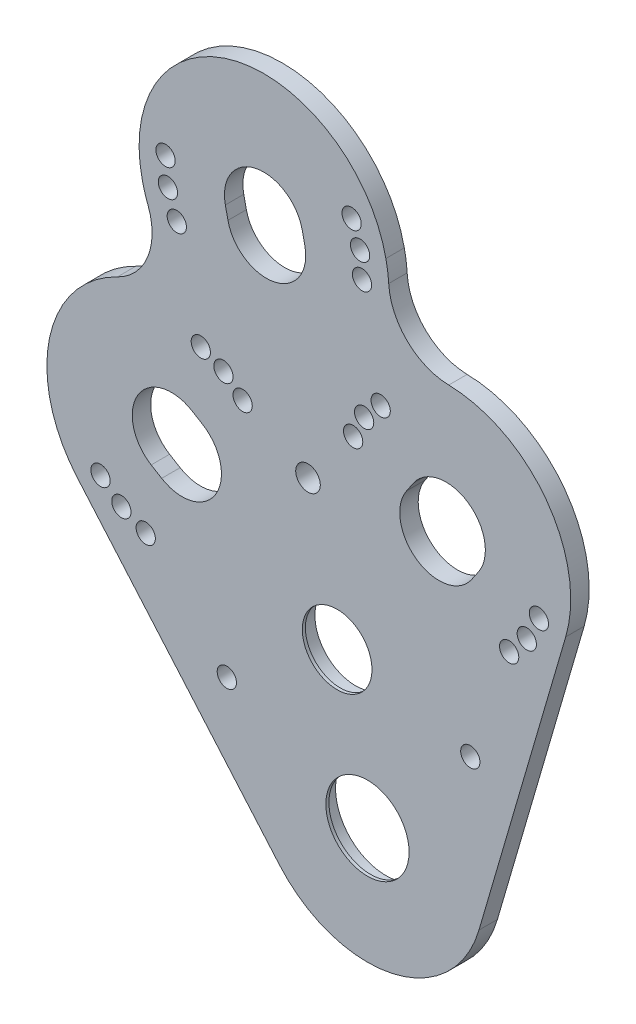
SolidWorks part; units mm, degrees
material "6061-T6 (SS)"
ref_plane "Front Plane" through (0, 0, 0) normal (0, 0, 1) x (1, 0, 0)
ref_plane "Top Plane" through (0, 0, 0) normal (0, 1, 0) x (1, 0, 0)
ref_plane "Right Plane" through (0, 0, 0) normal (1, 0, 0) x (0, 0, -1)
sketch "Sketch1" plane through (0, 0, 0) normal (0, 0, 1) x (1, 0, 0)
  line L0 (-7.8325, 36.0395) -> (0, 0) construction
  line L1 (-114.3559, 29.5275) -> (95.9028, 29.5275) construction
  line L2 (-107.2972, 26.9875) -> (95.9028, 26.9875) construction
  line L3 (-34.299, 122.3851) -> (-30.7317, 35.1036)
  line L4 (-107.2972, -23.8125) -> (95.9028, -23.8125) construction
  line L5 (-19.5919, 125.5814) -> (13.3895, 44.6925)
  line L6 (-55.9402, 56.7468) -> (-25.1916, 21.0759)
  line L7 (14.1715, 29.6307) -> (27.3408, 74.8464)
  line L8 (-50.1538, 61.7347) -> (-7.8325, 36.0395) construction
  line L9 (-7.8325, 36.0395) -> (-26.6659, 122.6971) construction
  line L10 (-7.8325, 36.0395) -> (20.0062, 76.9827) construction
  line L11 (-48.8132, 69.2556) -> (-16.6236, 63.5179)
  line L12 (-11.2396, 64.688) -> (15.6649, 83.2687)
  line L14 (-26.6659, 122.6971) -> (-26.7738, 123.1935) construction
  line L15 (-50.1538, 61.7347) -> (-50.588, 61.9983) construction
  line L16 (-22.7158, -19.6015) -> (-74.972, 40.9574)
  line L17 (28.8025, -8.4049) -> (51.2095, 68.3806)
  line L18 (-51.5405, 117.551) -> (-1.8993, 128.3396) construction
  line L19 (-49.2446, 111.0625) -> (-4.0872, 134.3316) construction
  line L20 (-52.1448, 124.407) -> (-1.4028, 121.9799) construction
  line L21 (3.4137, 96.2141) -> (36.5986, 57.7512) construction
  line L22 (-57.2674, 37.3512) -> (-43.0402, 86.1182) construction
  line L23 (-68.9403, 44.4384) -> (-32.2357, 79.5583) construction
  line L24 (-37.1888, 83.5781) -> (-63.553, 40.155) construction
  line L25 (-50.588, 61.9983) -> (-47.8741, 60.3506) construction
  line L26 (-45.3152, 70.683) -> (-42.6012, 69.0352)
  line L27 (-55.8609, 53.3137) -> (-53.1469, 51.666)
  line L28 (-26.7738, 123.1935) -> (-26.0995, 120.0909) construction
  line L29 (-16.8456, 125.3512) -> (-16.1713, 122.2486)
  line L30 (-36.702, 121.0358) -> (-36.0278, 117.9332)
  line L31 (20.0062, 76.9827) -> (20.2918, 77.4027) construction
  line L32 (-0.8556, 91.4744) -> (41.1535, 62.911) construction
  line L33 (-3.6935, 85.7615) -> (44.277, 69.044) construction
  line L34 (20.2918, 77.4027) -> (18.5066, 74.7772) construction
  line L35 (28.6936, 71.6901) -> (26.9084, 69.0645)
  line L36 (11.89, 83.1154) -> (10.1047, 80.4899)
  circle A0 centre (0, 0) radius 27.94 construction
  circle A1 centre (-7.8325, 36.0395) radius 15.24 construction
  circle A2 centre (-7.8325, 36.0395) radius 8.89 construction
  circle A3 centre (0, 0) radius 21.59 construction
  circle A4 centre (-50.1538, 61.7347) radius 32.2072 construction
  circle A5 centre (20.0062, 76.9827) radius 32.2072 construction
  circle A6 centre (-26.6659, 122.6971) radius 32.2072
  arc A7 (-25.1916, 21.0759) -> (14.1715, 29.6307) centre (-7.8325, 36.0395) ccw
  arc A8 (-48.8132, 69.2556) -> (-55.9402, 56.7468) centre (-50.1538, 61.7347) ccw
  arc A9 (27.3408, 74.8464) -> (15.6649, 83.2687) centre (20.0062, 76.9827) ccw
  arc A10 (-19.5919, 125.5814) -> (-34.299, 122.3851) centre (-26.6659, 122.6971) ccw
  circle A11 centre (-15.3533, 70.6445) radius 3.175
  arc A12 (-16.6236, 63.5179) -> (-11.2396, 64.688) centre (-15.3533, 70.6445) ccw
  arc A13 (-30.7317, 35.1036) -> (13.3895, 44.6925) centre (-7.8325, 36.0395) ccw
  circle A14 centre (-26.7738, 123.1935) radius 32.2072
  circle A15 centre (-26.7199, 122.9453) radius 32.2072 construction
  circle A16 centre (-50.588, 61.9983) radius 32.2072
  circle A17 centre (-50.3709, 61.8665) radius 32.2072 construction
  arc A18 (5.4875, 124.5569) -> (20.9913, 109.6024) centre (21.336, 125.4736) ccw
  arc A19 (-64.5891, 91.0031) -> (-56.6909, 111.0436) centre (-71.4903, 105.2995) ccw
  circle A20 centre (-36.3191, 15.6028) radius 9.525 construction
  circle A21 centre (26.5668, 29.2699) radius 9.525 construction
  arc A22 (-22.7158, -19.6015) -> (28.8025, -8.4049) centre (0, 0) ccw
  circle A23 centre (-7.8325, 36.0395) radius 10.5
  circle A24 centre (0, 0) radius 13
  circle A25 centre (0, 0) radius 8.5 construction
  circle A26 centre (0, 0) radius 12 construction
  circle A27 centre (-7.8325, 36.0395) radius 8.5 construction
  arc A28 (-45.3152, 70.683) -> (-55.8609, 53.3137) centre (-50.588, 61.9983) ccw
  arc A29 (-53.1469, 51.666) -> (-42.6012, 69.0352) centre (-47.8741, 60.3506) ccw
  arc A30 (-16.8456, 125.3512) -> (-36.702, 121.0358) centre (-26.7738, 123.1935) ccw
  arc A31 (-36.0278, 117.9332) -> (-16.1713, 122.2486) centre (-26.0995, 120.0909) ccw
  arc A32 (28.6936, 71.6901) -> (11.89, 83.1154) centre (20.2918, 77.4027) ccw
  circle A33 centre (-15.3533, 70.6445) radius 3.7158 construction
  arc A34 (-69.7639, 36.1219) -> (-70.3006, 35.5438) centre (-70.0002, 35.803) ccw
  circle A35 centre (20.149, 77.1927) radius 32.2072 construction
  circle A36 centre (20.2918, 77.4027) radius 32.2072
  arc A37 (10.1047, 80.4899) -> (26.9084, 69.0645) centre (18.5066, 74.7772) ccw
  arc A38 (49.2064, 61.5164) -> (48.4781, 61.8196) centre (48.8254, 61.6276) ccw
  circle A39 centre (-7.8325, 36.0395) radius 9
  circle A40 centre (0, 0) radius 10.75
  point P64 (-26.7199, 122.9453)
  point P66 (-51.5405, 117.551)
  point P67 (-1.8993, 128.3396)
  point P69 (-26.6659, 122.6971)
  point P71 (-49.2446, 111.0625)
  point P72 (-4.0872, 134.3316)
  point P74 (-26.7738, 123.1935)
  point P76 (-52.1448, 124.407)
  point P77 (-1.4028, 121.9799)
  point P79 (20.0062, 76.9827)
  point P81 (3.4137, 96.2141)
  point P82 (36.5986, 57.7512)
  point P88 (-50.588, 61.9983)
  point P89 (-68.9403, 44.4384)
  point P90 (-57.2674, 37.3512)
  point P91 (-63.553, 40.155)
  point P92 (-37.1888, 83.5781)
  point P93 (-43.0402, 86.1182)
  point P94 (-32.2357, 79.5583)
  point P95 (-50.3709, 61.8665)
  point P96 (-50.1538, 61.7347)
  point P98 (-49.231, 61.1745)
  point P104 (-26.4367, 121.6422)
  point P120 (20.149, 77.1927)
  point P121 (20.2918, 77.4027)
  point P122 (19.3992, 76.09)
  point P123 (-0.8556, 91.4744)
  point P124 (-3.6935, 85.7615)
  point P125 (41.1535, 62.911)
  point P126 (44.277, 69.044)
  point P135 (-36.3191, 15.6028)
  point P136 (26.5668, 29.2699)
  point P137 (-15.3533, 70.6445)
  dimension "D1" = 55.88
  dimension "D2" = 43.18
  dimension "D3" = 17.78
  dimension "D4" = 30.48
  dimension "D10" = 64.4144
  dimension "D11" = 45.8366
  dimension "D12" = 15.2789
  dimension "D16" = 92.949
  dimension "D18" = 6.35
  dimension "D19" = 14.478
  dimension "D20" = 252
  dimension "D9" = 45.8366
  dimension "D23" = 0.254
  dimension "D22" = 276
  dimension "D25" = 31.75
  dimension "D26" = 30.0037
  dimension "D27" = 19.05
  dimension "D31" = 26
  dimension "D30" = 21
  dimension "D32" = 17
  dimension "D33" = 24
  dimension "D34" = 17
  dimension "D38" = 15
  dimension "D40" = 10.16
  dimension "D42" = 10.16
  dimension "D44" = 15
  dimension "D45" = 0.7937
  dimension "D49" = 10.16
  dimension "D50" = 0.7937
  dimension "D51" = 18
  dimension "D52" = 21.5
  dimension "D5" = 36.8808
  dimension "D6" = 26.9875
  dimension "D7" = 50.8
  dimension "D8" = 2.54
  dimension "D13" = 49.5109
  dimension "D14" = 49.5109
  dimension "D15" = 123
  dimension "D17" = 46.475
  dimension "D21" = 140.868
  dimension "D24" = 0.254
  dimension "D28" = 12.7
  dimension "D29" = 12.7
  dimension "D35" = 50.8
  dimension "D36" = 15
  dimension "D37" = 15
  dimension "D39" = 15
  dimension "D41" = 3.175
  dimension "D43" = 3.175
  dimension "D46" = 0.254
  dimension "D47" = 15
  dimension "D48" = 3.175
extrude "Boss-Extrude4" add sketch "Sketch1" against normal blind 4.7625 contours A29 L11 L3 A16 L6 L27 A28 L26 | A19 A16 L3 A6 | A31 L30 A30 L29 L5 A14 A6 L3 | A31 L3 A14 L5 | A36 A18 A6 L5 | A36 L5 A6 L3 A16 L11 A12 L12 A11 | A37 L36 A32 L35 L7 A36 L5 L12 | A37 L12 L5 A36 L7 | L5 A36 L12 | L12 A36 L5 | L11 A16 L3 | L3 A16 L11 | A29 L6 A16 L3 L11 | A36 L12 A12 L11 A16 L3 A13 A7 L5 A23 | L17 A38 A36 L7 A7 L6 A16 A34 L16 A22 A24 | A36 L5 A13 L7 | A16 L6 A13 L3 | A14 L3 A6 L5 | A14 A6 L3 | A14 L5 A6 | A6 A14 | A34 A16 L16 | A38 L17 A36 region at (-22.1177, 101.7694, 0) region at (-34.3926, 102.5795, 0) region at (-19.8784, 91.4659, 0) region at (-33.3854, 91.348, 0) region at (-17.8563, 82.1616, 0) region at (-51.0886, 97.2563, 0) region at (-33.5979, 154.5928, 0) region at (1.9221, 108.4912, 0) region at (-26.7792, 74.2557, 0) region at (-33.2881, 77.5636, 0) region at (6.1131, 109.688, 0) region at (-26.0427, 53.9476, 0) region at (-37.1264, 49.3079, 0) region at (-17.6511, 62.9919, 0) region at (5.4569, 104.9987, 0) region at (-6.4568, 78.6724, 0) region at (-31.6587, 31.2303, 0) region at (-71.4587, 37.2183, 0) region at (13.3118, 60.2697, 0) region at (1.3021, 59.8905, 0) region at (-31.6403, 26.2453, 0) region at (15.8405, 41.5534, 0) region at (49.565, 63.5205, 0)
hole_wizard "#10 Clearance Hole3" positions "Sketch10" profile "Sketch9" hole size "#10" standard "ANSI Inch" end condition through all
sketch "Sketch10" plane through (0, 0, 0) normal (0, 0, 1) x (1, 0, 0)
  point P0 (3.4137, 96.2141)
  point P3 (-43.0402, 86.1182)
  point P6 (-37.1888, 83.5781)
  point P9 (-32.2357, 79.5583)
  point P12 (-3.6935, 85.7615)
  point P15 (-0.8556, 91.4744)
  point P18 (36.5986, 57.7512)
  point P21 (41.1535, 62.911)
  point P24 (44.277, 69.044)
  point P27 (26.5668, 29.2699)
  point P30 (-36.3191, 15.6028)
  point P33 (-57.2674, 37.3512)
  point P36 (-63.553, 40.155)
  point P39 (-68.9403, 44.4384)
  point P42 (-49.2446, 111.0625)
  point P45 (-51.5405, 117.551)
  point P48 (-52.1448, 124.407)
  point P51 (-1.4028, 121.9799)
  point P54 (-1.8993, 128.3396)
  point P57 (-4.0872, 134.3316)
sketch "Sketch9" plane through (3.4137, 96.2141, 0) normal (1, 0, 0) x (0, -1, 0)
  line L0 (0, 0) -> (0, 4.7625)
  line L1 (0, 4.7625) -> (2.4892, 4.7625)
  line L2 (2.4892, 4.7625) -> (2.4892, 0)
  line L5 (2.4892, 0) -> (0, 0)
  line L11 (0, -6.35) -> (0, 107.95) construction
  dimension "Thru Hole Dia." = 4.9784
  dimension "Thru Hole Depth" = 4.7625
extrude "Boss-Extrude5" add sketch "Sketch1<13>" against normal blind 0.7937 contours A23 A39 | A24 A40 region at (-18.0355, 36.0395, 0) region at (-12.6323, 0, 0)
sketch "Sketch1<13>" plane through (0, 0, 0) normal (0, 0, 1) x (1, 0, 0) same geometry as "Sketch1"
equation "\"D1@Sketch1\"=44/20"
equation "\"D2@Sketch1\"=34/20"
equation "\"D3@Sketch1\"=14/20"
equation "\"D4@Sketch1\"=24/20"
equation "\"D5@Sketch1\"=(14+44)/20/2 + .002"
equation "\"D11@Sketch1\"=48*3mm/pi"
equation "\"D12@Sketch1\"=16*3mm/pi"
equation "\"D13@Sketch1\"=(\"D10@Sketch1\"+\"D4@Sketch1\"+.1)/2+1/32"
equation "\"D14@Sketch1\"=\"D13@Sketch1\""
equation "\"D16@Sketch1\"=\"D17@Sketch1\""
equation "\"D17@Sketch1\"=\"D16@Sketch1\"/2"
equation "\"D20@Sketch1\"=252mm"
equation "\"D19@Sketch1\"=0.50in+.035*2"
equation "\"D22@Sketch1\"=92*3mm"
equation "\"D9@Sketch1\"=\"D11@Sketch1\""
equation "\"D26@Sketch1\"=(46/20)/2+1/32"
equation "\"D31@Sketch1\"=26mm"
equation "\"D30@Sketch1\"=21mm"
equation "\"D32@Sketch1\"=17mm"
equation "\"D33@Sketch1\"=24mm"
equation "\"D34@Sketch1\"=17mm"
equation "\"D36@Sketch1\"=\"D37@Sketch1\""
equation "\"D44@Sketch1\"=\"D47@Sketch1\""
equation "\"D47@Sketch1\"=\"D36@Sketch1\""
equation "\"D39@Sketch1\"=\"D38@Sketch1\""
equation "\"D38@Sketch1\"=\"D36@Sketch1\""
equation "\"D52@Sketch1\"=(26mm+17mm)/2"
equation "\"D51@Sketch1\"=18mm"
